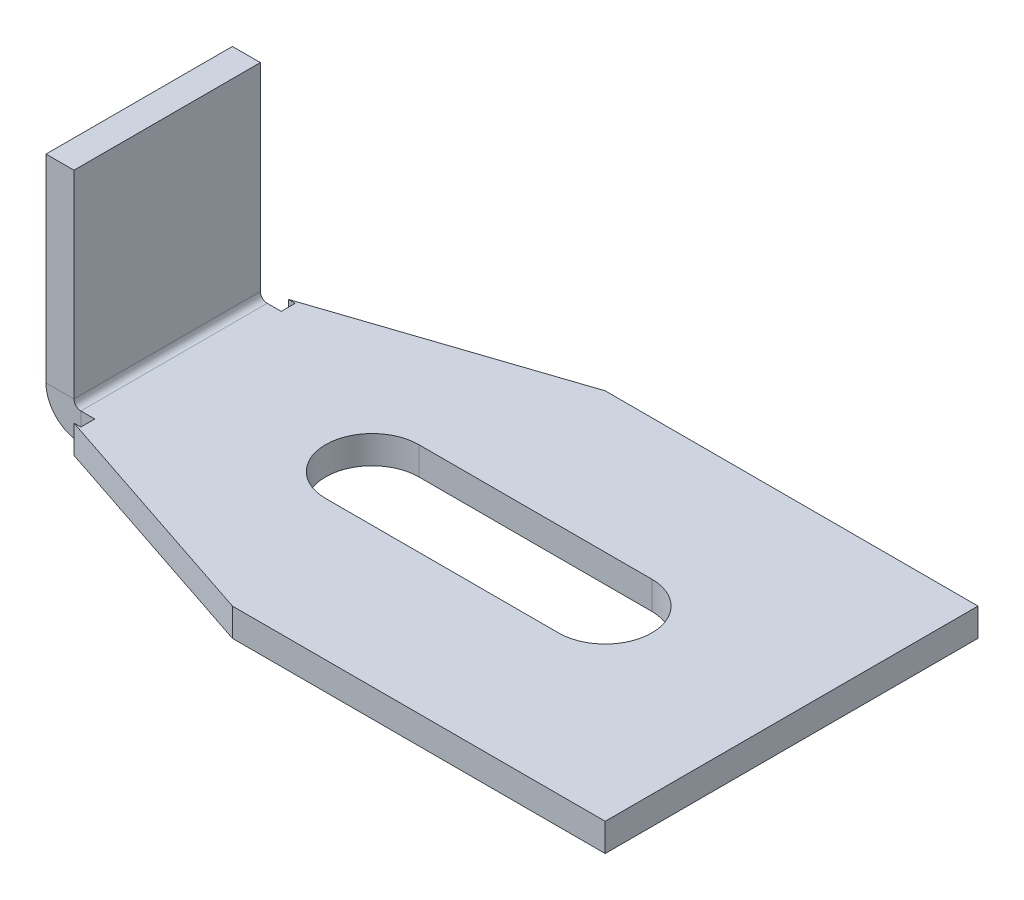
SolidWorks part; units mm, degrees
note: The reader was unsure of these and kept them because the rebuilt part matched: flange length of "Edge-Flange1".
material "ASTM A36 Steel"
ref_plane "Front Plane" through (0, 0, 0) normal (0, 0, 1) x (1, 0, 0)
ref_plane "Top Plane" through (0, 0, 0) normal (0, 1, 0) x (1, 0, 0)
ref_plane "Right Plane" through (0, 0, 0) normal (1, 0, 0) x (0, 0, -1)
sketch "Sketch1" plane through (0, 0, 0) normal (0, 1, 0) x (1, 0, 0)
  line L0 (0, 0) -> (0, 10)
  line L1 (0, 0) -> (0, -10)
  line L2 (0, 0) -> (70, 0) construction
  line L3 (70, 0) -> (70, 20)
  line L4 (70, 0) -> (70, -20)
  line L5 (70, -20) -> (30, -20)
  line L6 (70, 20) -> (30, 20)
  line L7 (30, 20) -> (0, 10)
  line L8 (30, -20) -> (0, -10)
base flange "Base-Flange1" sketch "Sketch1" thickness 3 reverse thickness direction no parameters "D1"=0.7366
edge flange "Edge-Flange1" sketch "Sketch8" flange angle 90 flange length 25 flange position material inside bend radius 0.7366 thickness 3 relief rectangular parameters "D6"=10
sketch "Sketch8" plane through (0, 0, 0) normal (-1, 0, 0) x (0, 0, 1)
  line L2 (-10, 0) -> (-10, 22)
  line L3 (-10, 22) -> (10, 22)
  line L4 (10, 22) -> (10, 0)
  line L5 (-10, 0) -> (10, 0) construction
  line L6 (-10, 0) -> (10, 0)
bend "EdgeBend1" bend radius 0.7366 bend angle 90 parameters "D5"=1
sketch "Sketch9" plane through (0, 0, 0) normal (0, 1, 0) x (1, 0, 0)
  line L0 (50, 0) -> (25, 0) construction
  line L1 (50, -5) -> (25, -5)
  line L2 (50, 5) -> (25, 5)
  line L3 (70, -20) -> (70, 20) construction
  arc A0 (50, -5) -> (50, 5) centre (50, 0) ccw
  arc A1 (25, 5) -> (25, -5) centre (25, 0) ccw
  point P3 (37.5, 0)
  dimension "D1" = 5
  dimension "D2" = 25
  dimension "D3" = 20
extrude "Cut-Extrude1" cut sketch "Sketch9" against normal blind 10 normal cut yes
sketch "Bend-Lines1" [suppressed] plane through (0, 0, 0) normal (0, 1, 0) x (1, 0, 0)
sketch "Bounding-Box1" [suppressed] plane through (0, 0, 0) normal (0, 1, 0) x (1, 0, 0)
sheet metal parameters "Sheet-Metal1" thickness 3 parameters "D1"=0.7366
flat pattern "Flat-Pattern1" [suppressed]
sketch "Bend-Lines2" plane through (0, 0, 0) normal (0, 1, 0) x (1, 0, 0)
sketch3d "Bounding-Box2" [suppressed]
  line L0 (-70, 20, 0) -> (0, 20, 0) construction
  line L1 (-70, -20, 0) -> (0, -20, 0) construction
  line L2 (-70, 20, 0) -> (-70, -20, 0) construction
  line L3 (0, 20, 0) -> (0, -20, 0) construction
sheet metal parameters "Sheet-Metal2" thickness 3 parameters "D1"=0.7366
flat pattern "Flat-Pattern1"
sketch "Bend-Lines2" plane through (0, 0, 0) normal (0, 1, 0) x (1, 0, 0)
  line L0 (1.98, 10) -> (1.98, -10) construction
  line L1 (1.98, 10) -> (1.98, -10) construction
sketch3d "Bounding-Box2" [suppressed]
  line L0 (70, 20, 0) -> (-21.04, 20, 0) construction
  line L1 (70, -20, 0) -> (-21.04, -20, 0) construction
  line L2 (70, 20, 0) -> (70, -20, 0) construction
  line L3 (-21.04, 20, 0) -> (-21.04, -20, 0) construction
bend of the flat pattern "Flatten-<EdgeBend1>1"
sheet metal parameters "Sheet-Metal3" thickness 3 parameters "D1"=0.7366
flat pattern "Flat-Pattern1"
sketch "Bend-Lines2" plane through (0, 0, 0) normal (0, 1, 0) x (1, 0, 0)
  line L0 (1.98, 10) -> (1.98, -10) construction
  line L1 (1.98, 10) -> (1.98, -10) construction
sketch3d "Bounding-Box2" [suppressed]
  line L0 (70, 20, 0) -> (-21.04, 20, 0) construction
  line L1 (70, -20, 0) -> (-21.04, -20, 0) construction
  line L2 (70, 20, 0) -> (70, -20, 0) construction
  line L3 (-21.04, 20, 0) -> (-21.04, -20, 0) construction
bend of the flat pattern "Flatten-<EdgeBend1>1"
